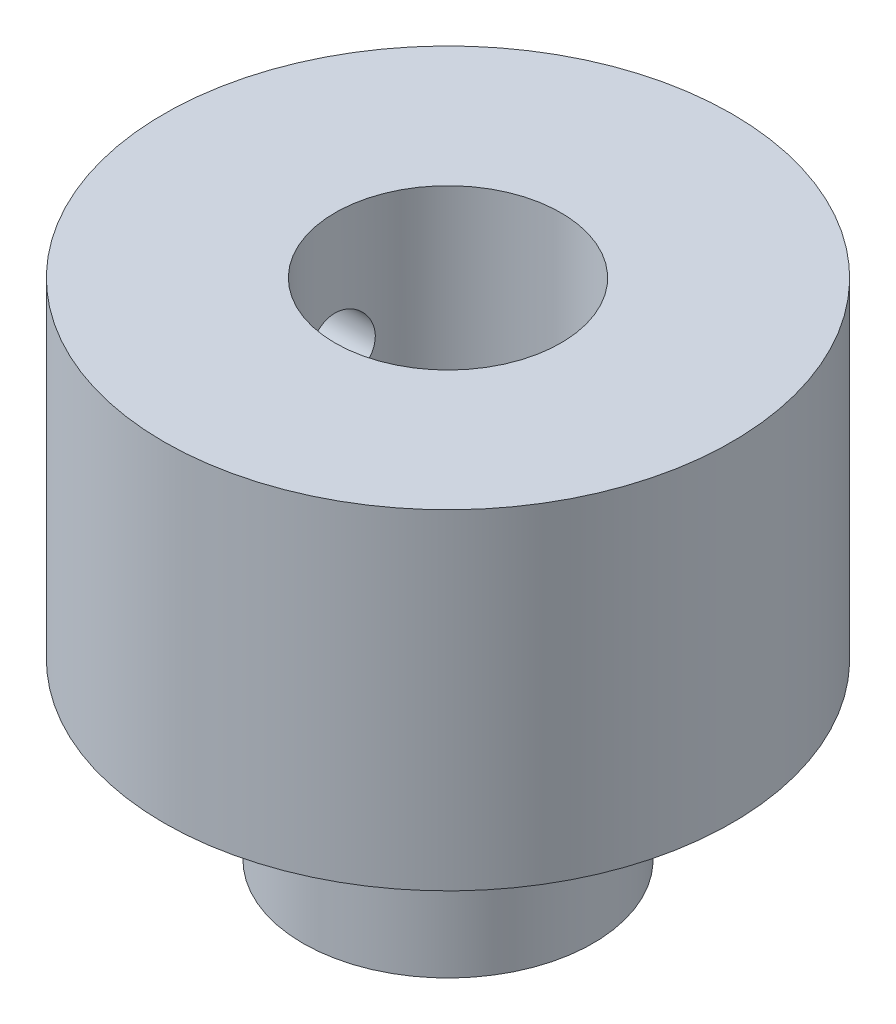
SolidWorks part; units mm, degrees
ref_plane "Front Plane" through (0, 0, 0) normal (0, 0, 1) x (1, 0, 0)
ref_plane "Top Plane" through (0, 0, 0) normal (0, 1, 0) x (1, 0, 0)
ref_plane "Right Plane" through (0, 0, 0) normal (1, 0, 0) x (0, 0, -1)
sketch "Sketch1" plane through (0, 0, 0) normal (0, 1, 0) x (1, 0, 0)
  circle A0 centre (0, 0) radius 3.25
  circle A1 centre (0, 0) radius 8.175
  circle A2 centre (0, 0) radius 8.175
  point P25 (0, 0)
extrude "Boss-Extrude1" add sketch "Sketch1" along normal blind 6.5 and the other way blind 3 contours A1 A0 region at (-7.9438, 0, 0)
extrude "Boss-Extrude2" add sketch "Sketch1<3>" against normal blind 3 separate body contours A2 A1 region at (-7.9438, 0, 0)
sketch "Sketch1<3>" plane through (0, 0, 0) normal (0, 1, 0) x (1, 0, 0) same geometry as "Sketch1"
sketch "Sketch2" plane through (0, 0, 0) normal (1, 0, 0) x (0, 0, -1)
  line L0 (0, 2) -> (0, 0)
  circle A0 centre (0, 3) radius 1
  dimension "D1" = 2
  dimension "D3" = 2
  dimension "D2" = 2
extrude "Cut-Extrude1" cut sketch "Sketch2" against normal blind 15 contours A0
sketch "Sketch3" plane through (0, -3, 0) normal (0, -1, 0) x (1, 0, 0)
  circle A1 centre (0, 11.7973) radius 1
  circle A2 centre (9.2235, 7.3555) radius 1
  circle A3 centre (11.5015, -2.6252) radius 1
  circle A4 centre (5.1187, -10.629) radius 1
  circle A5 centre (-5.1187, -10.629) radius 1
  circle A6 centre (-11.5015, -2.6252) radius 1
  circle A7 centre (-9.2235, 7.3555) radius 1
  point P14 (0, 0)
  dimension "D1" = 7
extrude "Cut-Extrude2" [suppressed] cut sketch "Sketch3" against normal through all and the other way blind 3.175
sketch "Sketch4" plane through (0, -3, 0) normal (0, -1, 0) x (1, 0, 0)
  circle A0 centre (0, 0) radius 4.175
extrude "Boss-Extrude4" add sketch "Sketch4" along normal blind 5 contours A0
extrude "Cut-Extrude3" cut sketch "Sketch1<5>" against normal blind 13 and the other way blind 15 contours A0
sketch "Sketch1<5>" plane through (0, 0, 0) normal (0, 1, 0) x (1, 0, 0) same geometry as "Sketch1"
